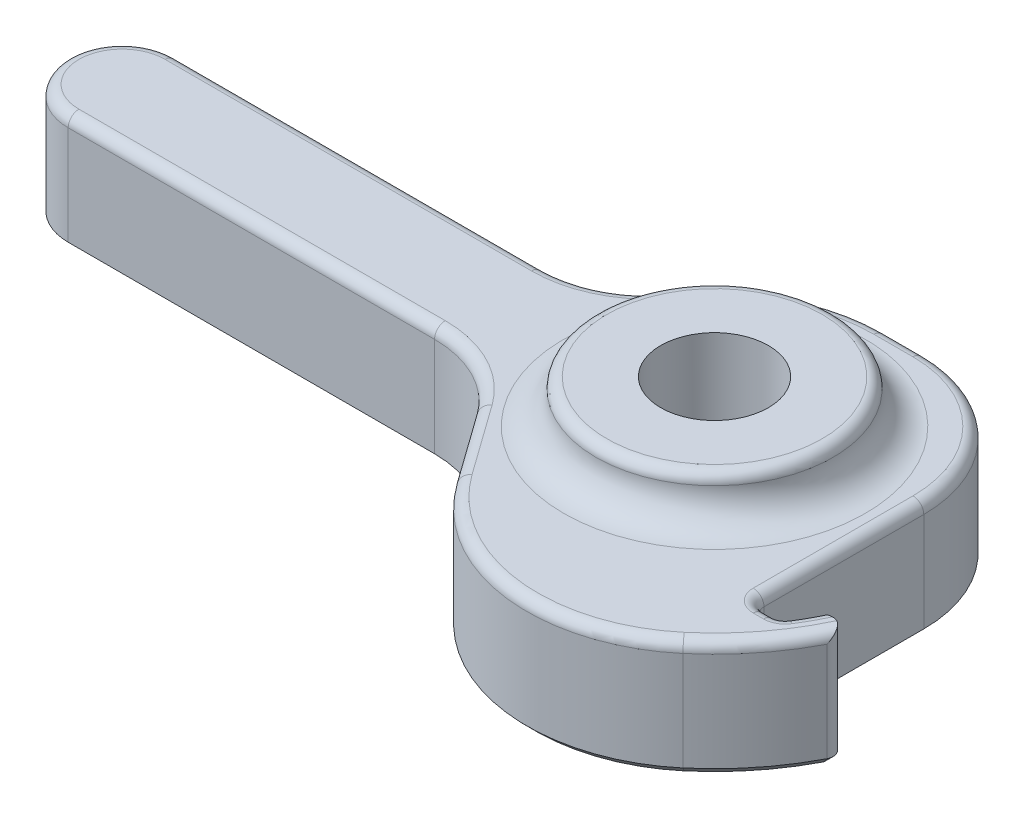
SolidWorks part; units mm, degrees
ref_plane "Front Plane" through (0, 0, 0) normal (0, 0, 1) x (1, 0, 0)
ref_plane "Top Plane" through (0, 0, 0) normal (0, 1, 0) x (1, 0, 0)
ref_plane "Right Plane" through (0, 0, 0) normal (1, 0, 0) x (0, 0, -1)
ref_plane "Plane1" through (0, -76.7336, 0) normal (0, -1, 0) x (-1, 0, 0)
sketch "Sketch1" plane through (0, -76.7336, 0) normal (0, 1, 0) x (1, 0, 0)
  line L0 (88.4412, 19.9) -> (88.4412, 13.8107) construction
  line L1 (88.4412, 19.9) -> (82.3519, 19.9) construction
  line L2 (53.0412, 9.5) -> (70.0455, 9.5)
  line L6 (80.5412, 12) -> (50.5412, 12) construction
  line L7 (53.0412, 14.5) -> (70.0455, 14.5)
  line L8 (86.6577, 18.1165) -> (86.1274, 17.5861) construction
  line L9 (82.3519, 19.9) -> (80.5412, 19.9)
  line L10 (88.4412, 13.8107) -> (88.4412, 12)
  line L11 (91.7588, 7.0779) -> (90.3785, 7.0779)
  line L12 (89.6912, 5.8945) -> (88.4412, 5.8945)
  line L13 (88.4412, 5.8945) -> (88.4412, 12)
  line L14 (74.1136, 7.407) -> (76.447, 4.1416)
  circle A0 centre (80.5412, 12) radius 2.5 construction
  circle A1 centre (80.5412, 12) radius 2.5
  arc A2 (80.5412, 19.9) -> (74.1136, 16.593) centre (80.5412, 12) ccw
  arc A3 (88.4412, 12) -> (80.5412, 19.9) centre (80.5412, 12) ccw construction
  arc A4 (53.0412, 14.5) -> (53.0412, 9.5) centre (53.0412, 12) ccw
  arc A5 (70.0455, 14.5) -> (74.1136, 16.593) centre (70.0455, 19.5) ccw
  arc A6 (70.0455, 9.5) -> (74.1136, 7.407) centre (70.0455, 4.5) cw
  arc A7 (53.0412, 9.5) -> (53.0412, 14.5) centre (53.0412, 12) ccw construction
  arc A8 (74.1136, 16.593) -> (74.1136, 7.407) centre (80.5412, 12) ccw construction
  arc A14 (80.5412, 4.1) -> (88.4412, 12) centre (80.5412, 12) ccw construction
  circle A15 centre (80.5412, 12) radius 7.9 construction
  circle A16 centre (80.5412, 12) radius 12.25 construction
  arc A17 (88.4412, 13.8107) -> (82.3519, 19.9) centre (82.3519, 13.8107) ccw
  circle A18 centre (80.5412, 12) radius 11 construction
  arc A19 (90.3785, 7.0779) -> (89.6912, 5.8945) centre (80.5412, 12) cw
  arc A20 (91.7588, 7.0779) -> (88.4412, 2.6377) centre (80.5412, 12) cw
  arc A21 (88.4412, 2.6377) -> (76.447, 4.1416) centre (83.1379, 8.9227) cw
  dimension "D1" = 5
  dimension "D2" = 5
  dimension "D4" = 0.75
  dimension "D6" = 22
  dimension "D7" = 24.5
  dimension "D8" = 4.9221
  dimension "D3" = 30
  dimension "D5" = 7.9
  dimension "D10" = 6.1055
extrude "Boss-Extrude1" add sketch "Sketch1" against normal blind 5.5 from offset 2 offset against normal yes
sketch "Sketch2" plane through (0, -76.7336, 0) normal (0, -1, 0) x (-1, 0, 0)
  circle A0 centre (-80.5412, 12) radius 2.5 construction
  circle A1 centre (-80.5412, 12) radius 2.5
  circle A2 centre (-80.5412, 12) radius 5.5
  dimension "D1" = 3
extrude "Boss-Extrude2" add sketch "Sketch2" along normal up to next
fillet "Fillet1" radius 1.5 1 edges at (80.5412, -78.7336, -6.5)
fillet "Fillet2" radius 0.5 19 edges at (90.0533, -78.7336, -6.4755) (89.0662, -78.7336, -5.8945) (90.3545, -78.7336, -4.6677) (82.1148, -78.7336, -0.763) (75.2803, -78.7336, -5.7743) (72.333, -78.7336, -8.9461) (61.5434, -78.7336, -9.5) (50.5412, -78.7336, -12) (61.5434, -78.7336, -14.5) (72.333, -78.7336, -15.0539) (76.927, -78.7336, -19.0248) (81.4465, -78.7336, -19.9) (86.6577, -78.7336, -18.1165) (80.5412, -76.7336, -17.5) (88.4412, -78.7336, -9.8526) (91.7588, -81.4836, -7.0779) (90.3785, -81.4836, -7.0779) (89.6912, -81.4836, -5.8945) (88.4412, -81.4836, -5.8945)
chamfer "Chamfer1" distance 0.4 angle 45 20 edges at (90.4257, -84.2336, -7.0067) (90.0484, -84.2336, -6.467) (89.6611, -84.2336, -5.9566) (89.1805, -84.2336, -5.8945) (88.5877, -84.2336, -6.0409) (88.4412, -84.2336, -10.1026) (86.6577, -84.2336, -18.1165) (81.4465, -84.2336, -19.9) (76.927, -84.2336, -19.0248) (72.333, -84.2336, -15.0539) (61.5434, -84.2336, -14.5) (50.5412, -84.2336, -12) (61.5434, -84.2336, -9.5) (72.333, -84.2336, -8.9461) (75.2803, -84.2336, -5.7743) (82.1148, -84.2336, -0.763) (90.1066, -84.2336, -4.3472) (91.3928, -84.2336, -6.8373) (90.8241, -84.2336, -7.0779) (80.5412, -84.2336, -9.5)
